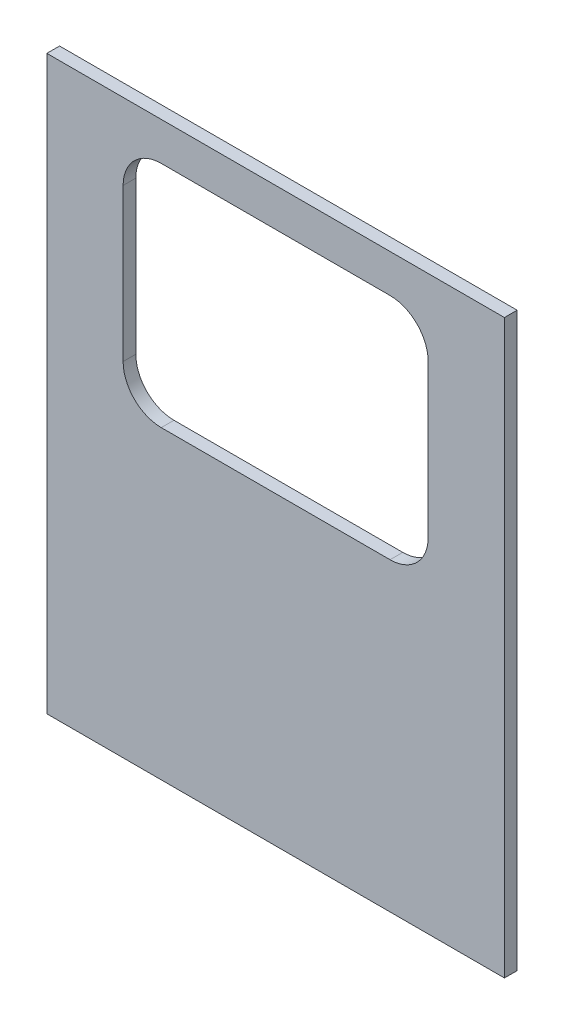
SolidWorks part; units mm, degrees
material "ABS PC"
ref_plane "Front Plane" through (0, 0, 0) normal (0, 0, 1) x (1, 0, 0)
ref_plane "Top Plane" through (0, 0, 0) normal (0, 1, 0) x (1, 0, 0)
ref_plane "Right Plane" through (0, 0, 0) normal (1, 0, 0) x (0, 0, -1)
sketch "Sketch1" plane through (0, 0, 0) normal (0, 0, 1) x (1, 0, 0)
  line L1 (-457.2, 571.5) -> (457.2, 571.5)
  line L2 (-457.2, 571.5) -> (-457.2, -571.5)
  line L3 (-457.2, -571.5) -> (457.2, -571.5)
  line L4 (457.2, 571.5) -> (457.2, -571.5)
  line L5 (-457.2, 571.5) -> (457.2, -571.5) construction
  line L6 (-457.2, -571.5) -> (457.2, 571.5) construction
  line L7 (-304.8, 495.3) -> (304.8, 495.3)
  line L8 (-304.8, 495.3) -> (-304.8, 38.1)
  line L9 (-304.8, 38.1) -> (304.8, 38.1)
  line L10 (304.8, 495.3) -> (304.8, 38.1)
  line L11 (-304.8, 495.3) -> (304.8, 38.1) construction
  line L12 (-304.8, 38.1) -> (304.8, 495.3) construction
  point P0 (0, 0)
  point P6 (0, 266.7)
  point P11 (0, 0)
  dimension "D1" = 457.2
  dimension "D2" = 609.6
  dimension "D3" = 609.6
  dimension "D4" = 76.2
  dimension "D5" = 914.4
extrude "Boss-Extrude1" add sketch "Sketch1" along normal blind 25.4
fillet "Fillet1" radius 76.2 4 edges at (304.8, 495.3, 12.7) (-304.8, 495.3, 12.7) (304.8, 38.1, 12.7) (-304.8, 38.1, 12.7)
